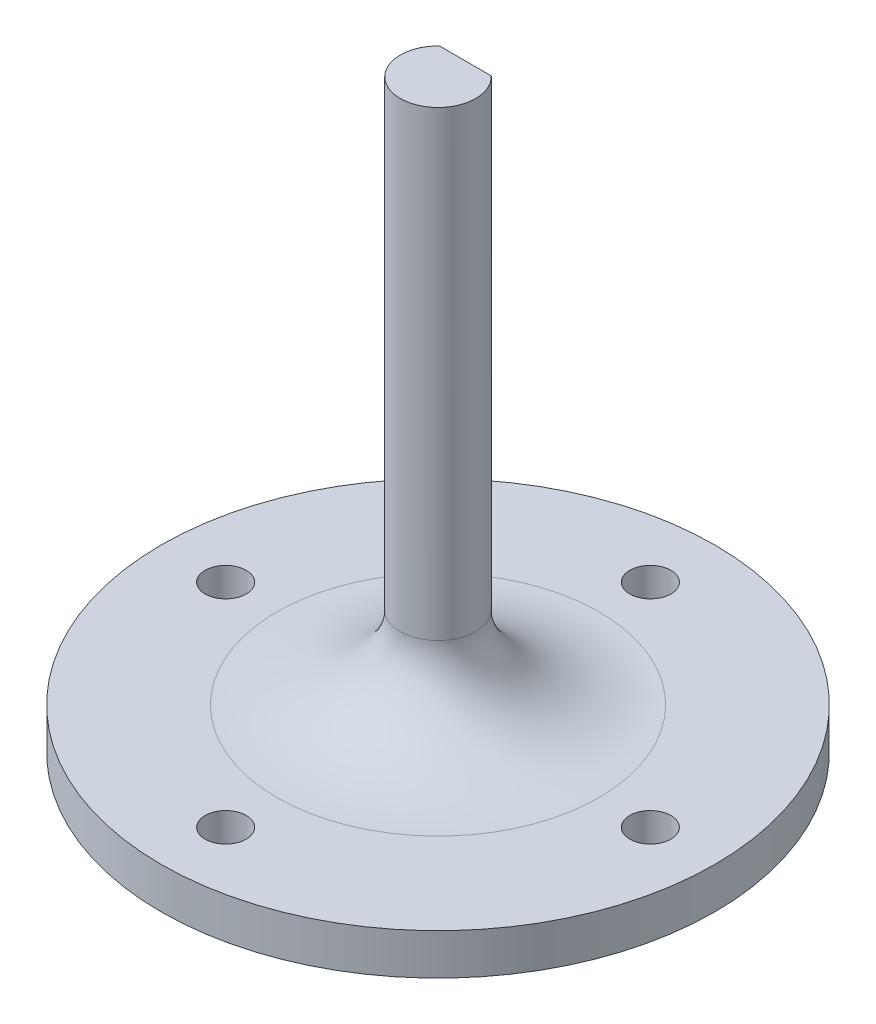
SolidWorks part; units mm, degrees
ref_plane "Front Plane" through (0, 0, 0) normal (0, 0, 1) x (1, 0, 0)
ref_plane "Top Plane" through (0, 0, 0) normal (0, 1, 0) x (1, 0, 0)
ref_plane "Right Plane" through (0, 0, 0) normal (1, 0, 0) x (0, 0, -1)
sketch "Sketch2" plane through (0, 0, 0) normal (0, 1, 0) x (1, 0, 0)
  line L0 (-1.8875, 2) -> (1.8875, 2)
  circle A0 centre (0, 0) radius 15.5 construction
  circle A1 centre (0, 15.5) radius 1.5
  circle A2 centre (-15.5, 0) radius 1.5
  circle A3 centre (0, -15.5) radius 1.5
  circle A4 centre (15.5, 0) radius 1.5
  circle A5 centre (0, 0) radius 2.75
  circle A6 centre (0, 0) radius 20.2034
  dimension "D2" = 3
  dimension "D3" = 5.5
  dimension "D1" = 15.5
  dimension "D4" = 2
extrude "Boss-Extrude1" add sketch "Sketch2" against normal blind 3 contours A6 A1 A2 A3 A4 A5 | L0 A5 | L0 A5 region at (0, 0, -2.3038) region at (0, 0, 0.2055) region at (-19.632, 0, 0)
extrude "Boss-Extrude2" add sketch "Sketch2<3>" along normal blind 39.7 contours L0 A5 region at (0, 0, 0.2055)
sketch "Sketch2<3>" plane through (0, 0, 0) normal (0, 1, 0) x (1, 0, 0) same geometry as "Sketch2"
extrude "Boss-Extrude3" add sketch "Sketch2<4>" along normal blind 6 contours L0 A5 region at (0, 0, -2.3038)
sketch "Sketch2<4>" plane through (0, 0, 0) normal (0, 1, 0) x (1, 0, 0) same geometry as "Sketch2"
chamfer "Chamfer1" [suppressed] distance 9 distance2 6
fillet "Fillet1" radius 9 1 edges at (0, 0, 2.75) second distance 6 first distance on face at (0, 0, 20.2034)
fillet "Fillet2" [suppressed] radius 0.5
equation "\"largeBearOD\"= 21mm"
equation "\"largeBearID\" = 15mm"
equation "\"largeBearOTight\"= 0.34375mm'calibrate - hold onto gears"
equation "\"largeBearITight\"= 0mm'calibrate - hold onto eccentric nut"
equation "\"largeBearFlangeDiam\" = 22.5mm"
equation "\"largeBearFlangeWidth\" = 0.8mm"
equation "\"smallBearOD\"= 14.8mm"
equation "\"smallBearOTight\"= 0mm'calibrate - hold onto bottom of gearbox"
equation "\"smallBearOLoose\"= 0mm'calibrate - able to take off topHat"
equation "\"smallBearID\" = 10mm"
equation "\"smallBearITight\" = 0mm'hold onto "
equation "\"pinCircleDiam\"= 75mm"
equation "\"pinDiam\"= 6mm"
equation "\"sheetThickness\"= 0.1875in"
equation "\"ballBearDiam\"= 3.5mm"
equation "\"thrustBearingThickness\"= 5mm'measure this irl and change"
equation "\"thrustBearingID\"= 0mm'measure this irl and change"
equation "\"thrustBearingOD\"= 0mm'measure this irl and change"
equation "\"eccentricity\" = 1mm"
equation "\"dShaftDiam\"= 5mm"
